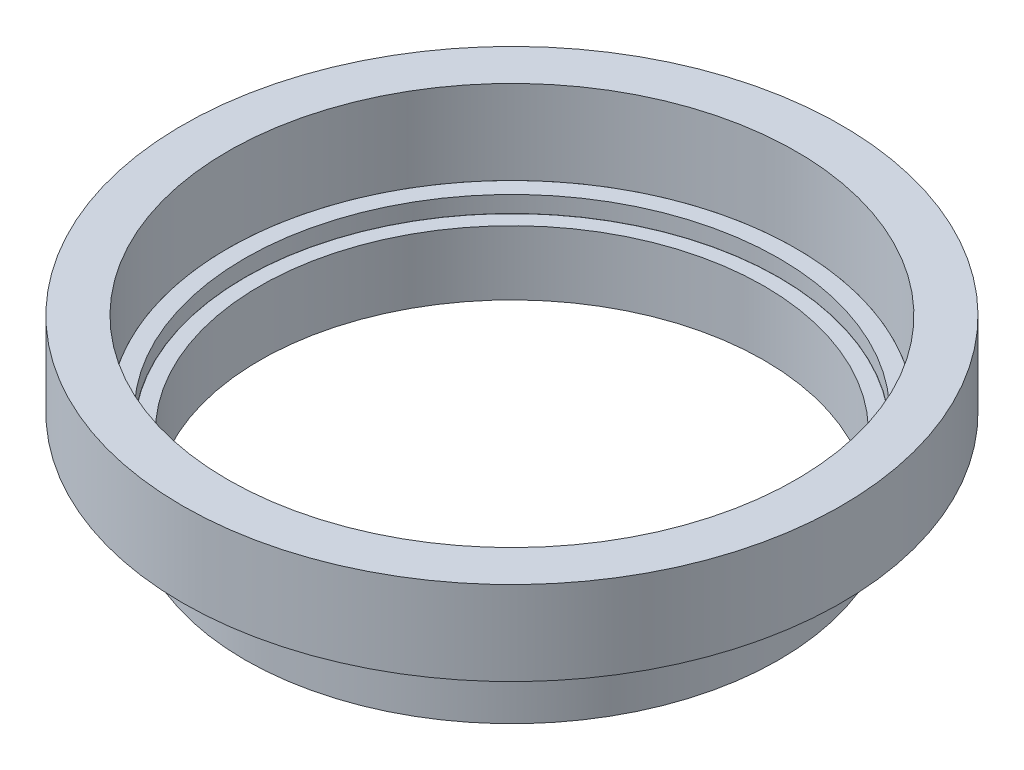
SolidWorks part; units mm, degrees
material "6061-T6 (SS)"
ref_plane "Front Plane" through (0, 0, 0) normal (0, 0, 1) x (1, 0, 0)
ref_plane "Top Plane" through (0, 0, 0) normal (0, 1, 0) x (1, 0, 0)
ref_plane "Right Plane" through (0, 0, 0) normal (1, 0, 0) x (0, 0, -1)
sketch "Sketch1" plane through (0, 0, 0) normal (0, 1, 0) x (1, 0, 0)
  circle A0 centre (0, 0) radius 50.8
  circle A1 centre (0, 0) radius 43.815
  dimension "D1" = 101.6
  dimension "D2" = 87.63
extrude "Boss-Extrude1" add sketch "Sketch1" against normal blind 12.954
ref_plane "Plane4" through (0, -15.494, 0) normal (0, -1, 0) x (-1, 0, 0)
sketch "Sketch2" plane through (0, -15.494, 0) normal (0, -1, 0) x (-1, 0, 0)
  circle A0 centre (0, 0) radius 41.1734
  circle A1 centre (0, 0) radius 43.815
  dimension "D1" = 82.3468
  dimension "D2" = 87.63
extrude "Boss-Extrude2" add sketch "Sketch2" against normal blind 2.54 separate body
ref_plane "Plane5" through (0, -18.034, 0) normal (0, -1, 0) x (-1, 0, 0)
sketch "Sketch3" plane through (0, -18.034, 0) normal (0, -1, 0) x (-1, 0, 0)
  circle A0 centre (0, 0) radius 38.862
  circle A1 centre (0, 0) radius 41.148
  dimension "D1" = 77.724
  dimension "D2" = 82.296
extrude "Boss-Extrude3" add sketch "Sketch3" against normal up to surface (2.54 mm away) and the other way blind 7.366 separate body up to face at (0, -15.494, -41.1734)
equation "\"0.39n\"=0.22"
